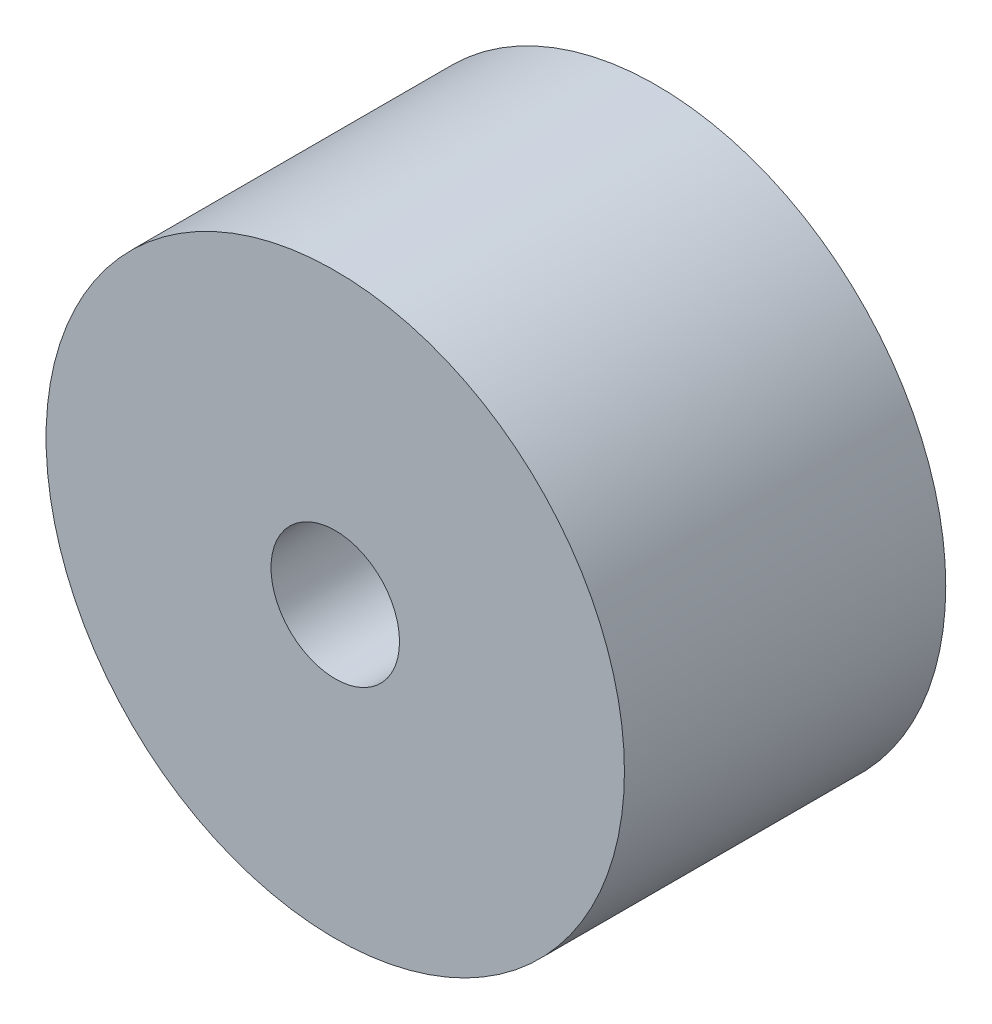
SolidWorks part; units mm, degrees
ref_plane "前视基准面" through (0, 0, 0) normal (0, 0, 1) x (1, 0, 0)
ref_plane "上视基准面" through (0, 0, 0) normal (0, 1, 0) x (1, 0, 0)
ref_plane "右视基准面" through (0, 0, 0) normal (1, 0, 0) x (0, 0, -1)
other "Configuration Table"
sketch "Sketch1" plane through (0, 0, 0) normal (0, 0, 1) x (1, 0, 0)
  circle A0 centre (0, 0) radius 18
extrude "Boss-Extrude1" add sketch "Sketch1" along normal blind 20
sketch "Sketch2" plane through (0, 0, 0) normal (0, 0, 1) x (1, 0, 0)
  circle A0 centre (0, 0) radius 4
extrude "Cut-Extrude1" cut sketch "Sketch2" along normal blind 20
ref_plane "bottom_face" through (0, 0, 0) normal (0, 0, 1) x (1, 0, 0)
sketch3d "3DSketch1"
  line L0 (0, 0, 0) -> (0, 0, 20) construction
ref_axis "center_axis" through (0, 0, 0) along (0, 0, 1)
